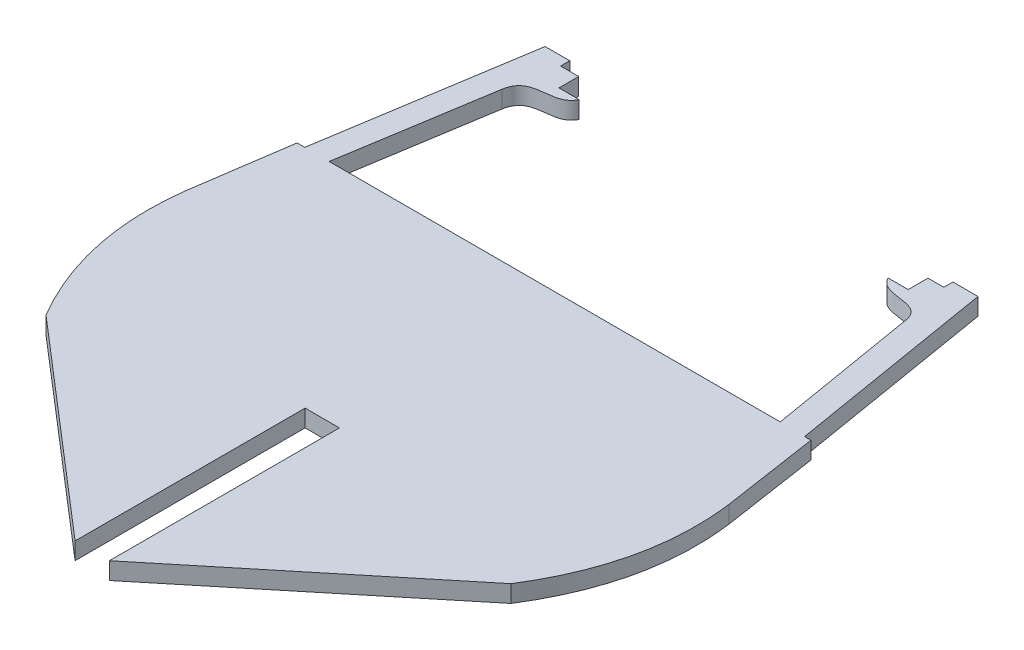
SolidWorks part; units mm, degrees
ref_plane "前视基准面" through (0, 0, 0) normal (0, 0, 1) x (1, 0, 0)
ref_plane "上视基准面" through (0, 0, 0) normal (0, 1, 0) x (1, 0, 0)
ref_plane "右视基准面" through (0, 0, 0) normal (1, 0, 0) x (0, 0, -1)
sketch "草图1" plane through (0, 0, 0) normal (0, 1, 0) x (1, 0, 0)
  line L0 (-191.5599, -195.3618) -> (-296.6831, -195.3618)
  line L1 (-296.6831, -195.3618) -> (-291.1353, -160.6526)
  line L2 (-191.5599, -195.3618) -> (-197.3921, -160.6526)
  line L3 (-180.8911, -217.9796) -> (-184.2867, -195.4832)
  line L5 (-184.2867, -195.4832) -> (-185.7637, -195.4832)
  line L6 (-185.7637, -195.4832) -> (-193.8359, -146.9965)
  line L7 (-193.8359, -146.9965) -> (-199.6681, -146.9965)
  line L8 (-199.6681, -146.9965) -> (-199.6681, -149.1303)
  line L9 (-199.6681, -149.1303) -> (-203.3667, -149.1303)
  line L10 (-203.3667, -149.1303) -> (-203.3667, -153.7361)
  line L11 (-203.3667, -153.7361) -> (-208.0609, -153.7361)
  line L12 (-302.3884, -195.3618) -> (-304.1767, -195.3618)
  line L13 (-304.1767, -195.3618) -> (-307.498, -217.9796)
  line L14 (-302.3884, -195.3618) -> (-294.724, -146.9965)
  line L15 (-294.724, -146.9965) -> (-288.9758, -146.9965)
  line L16 (-288.9758, -146.9965) -> (-288.9758, -149.1303)
  line L17 (-288.9758, -149.1303) -> (-284.7604, -149.1303)
  line L18 (-284.7604, -149.1303) -> (-284.7604, -153.7361)
  line L19 (-284.7604, -153.7361) -> (-280.034, -153.7361)
  line L20 (-190.2725, -259.3725) -> (-241.715, -301.5484)
  line L21 (-241.715, -301.5484) -> (-241.715, -247.9417)
  line L22 (-241.715, -247.9417) -> (-249.715, -247.9417)
  line L23 (-249.715, -247.9417) -> (-249.715, -301.5484)
  line L24 (-249.715, -301.5484) -> (-298.6721, -259.3725)
  spline S0 degree 3 poles (-208.0609, -153.7361) (-205.6538, -158.4575) (-198.1112, -154.1837) (-197.3921, -160.6526) knots 0 0 0 0 1 1 1 1
  spline S1 degree 3 poles (-280.034, -153.7361) (-282.3867, -158.4725) (-289.9755, -153.9633) (-291.1353, -160.6526) knots 0 0 0 0 1 1 1 1
  spline S2 degree 2 poles (-180.8911, -217.9796) (-178.0106, -239.8955) (-190.2725, -259.3725) knots 0 0 0 1 1 1
  spline S3 degree 2 poles (-307.498, -217.9796) (-310.2662, -239.7881) (-298.6721, -259.3725) knots 0 0 0 1 1 1
  dimension "D1" = 8
  dimension "D2" = 53.6067
extrude "凸台-拉伸1" add sketch "草图1" along normal blind 4
